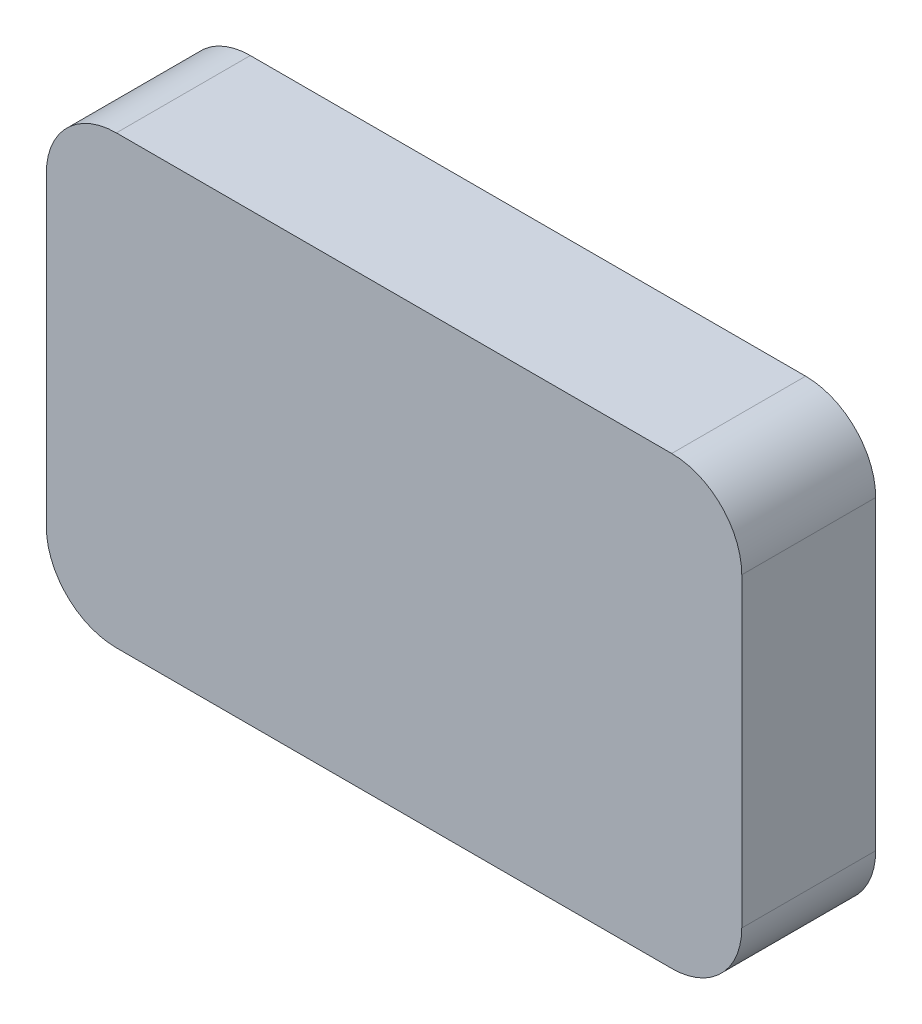
SolidWorks part; units mm, degrees
ref_plane "Plan de face" through (0, 0, 0) normal (0, 0, 1) x (1, 0, 0)
ref_plane "Plan de dessus" through (0, 0, 0) normal (0, 1, 0) x (1, 0, 0)
ref_plane "Plan de droite" through (0, 0, 0) normal (1, 0, 0) x (0, 0, -1)
sketch "Esquisse1" plane through (0, 0, 0) normal (0, 0, 1) x (1, 0, 0)
  line L1 (-39.6342, 31.8306) -> (39.6342, 31.8306)
  line L2 (-49.6342, 21.8306) -> (-49.6342, -21.8306)
  line L3 (-39.6342, -31.8306) -> (39.6342, -31.8306)
  line L4 (49.6342, 21.8306) -> (49.6342, -21.8306)
  line L5 (-49.6342, 31.8306) -> (49.6342, -31.8306) construction
  line L6 (-49.6342, -31.8306) -> (49.6342, 31.8306) construction
  arc A0 (-49.6342, -21.8306) -> (-39.6342, -31.8306) centre (-39.6342, -21.8306) ccw
  arc A1 (39.6342, -31.8306) -> (49.6342, -21.8306) centre (39.6342, -21.8306) ccw
  arc A2 (39.6342, 31.8306) -> (49.6342, 21.8306) centre (39.6342, 21.8306) cw
  arc A3 (-39.6342, 31.8306) -> (-49.6342, 21.8306) centre (-39.6342, 21.8306) ccw
  point P0 (0, 0)
  dimension "D1" = 10
sketch "profil" plane through (0, 0, 0) normal (1, 0, 0) x (0, 0, -1)
  line L0 (0, -30.2306) -> (9.1225, -30.2306)
  line L1 (9.1225, -30.2306) -> (17.9182, -25.6306)
  line L3 (17.9182, -31.8306) -> (0, -31.8306)
  line L4 (0, -31.8306) -> (0, -30.2306)
  line L6 (0, -21.8306) -> (0, -31.8306) construction
  line L7 (0, -31.8306) -> (0, 31.8306) construction
  line L8 (17.9182, -25.6306) -> (17.9182, -27.2306)
  line L9 (17.9182, -30.2306) -> (17.9182, -31.8306)
  arc A1 (17.9182, -27.2306) -> (17.9182, -30.2306) centre (17.9182, -28.7306) cw
  dimension "D1" = 3
  dimension "D2" = 1.6
sweep "Balayage1" add profiles "profil" path "Esquisse1"
extrude "Boss.-Extru.1" add sketch "Esquisse1<3>" along normal blind 1.2
sketch "Esquisse1<3>" plane through (0, 0, 0) normal (0, 0, 1) x (1, 0, 0) same geometry as "Esquisse1"
fillet "Congé1" radius 2 9 edges at (-45.5739, 27.7703, 0) (-48.0342, 0, 0) (-45.5739, -27.7703, 0) (-19.8171, -30.2306, 0) (19.8171, -30.2306, 0) (45.5739, -27.7703, 0) (48.0342, 0, 0) (45.5739, 27.7703, 0) (0, 30.2306, 0)
equation "\"buse\"=0.4"
equation "\"coque\"= \"buse\" * 4"
equation "\"diam_silicone\"=3"
equation "\"D1@profil\" = \"diam_silicone\""
equation "\"couche\"=0.2"
equation "\"D1@Boss.-Extru.1\"=\"fond\""
equation "\"fond\"= \"couche\" * 6"
